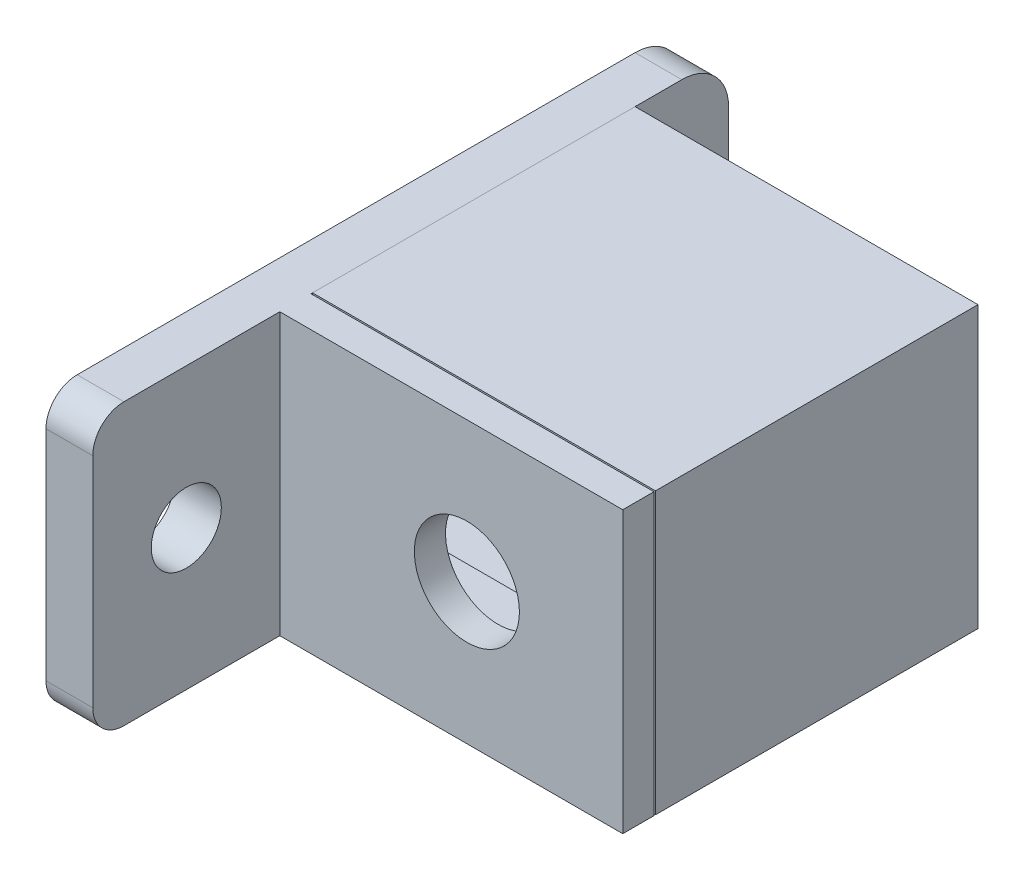
SolidWorks part; units mm, degrees
ref_plane "Front Plane" through (0, 0, 0) normal (0, 0, 1) x (1, 0, 0)
ref_plane "Top Plane" through (0, 0, 0) normal (0, 1, 0) x (1, 0, 0)
ref_plane "Right Plane" through (0, 0, 0) normal (1, 0, 0) x (0, 0, -1)
sketch "Sketch1" plane through (0, 0, 0) normal (1, 0, 0) x (0, 0, -1)
  line L1 (-13.46, 9) -> (-11.46, 9)
  line L2 (-13.46, 9) -> (-13.46, -9)
  line L3 (-13.46, -9) -> (-11.46, -9)
  line L4 (-11.46, 9) -> (-11.46, -9)
  line L5 (0, 0) -> (-11.46, 0) construction
  line L6 (-13.46, -6) -> (-13.46, 6) construction
  line L7 (-13.46, -6) -> (-13.46, 6) construction
  line L8 (4.33, 1.135) -> (4.33, -1.135) construction
  line L9 (4.33, 1.135) -> (4.33, -1.135) construction
  dimension "D1" = 3
  dimension "D2" = 2
extrude "Boss-Extrude1" add sketch "Sketch1" along normal blind 10 and the other way blind 15
sketch "Sketch2" plane through (0, 0, 11.46) normal (0, 0, -1) x (-1, 0, 0)
  line L0 (15, -9) -> (15, 9) construction
  line L1 (15, 9) -> (12, 9)
  line L2 (15, 9) -> (15, -9)
  line L3 (15, -9) -> (12, -9)
  line L4 (12, 9) -> (12, -9)
  line L5 (15, -9) -> (-10, -9) construction
  dimension "D1" = 3
extrude "Boss-Extrude2" add sketch "Sketch2" along normal offset from surface (20.79 mm away) 5 offset beyond the face yes
sketch "Sketch3" plane through (-12, 0, 0) normal (1, 0, 0) x (0, 0, -1)
  line L0 (-11.36, 9) -> (-11.36, 7)
  line L1 (-11.46, 9) -> (-11.46, -9) construction
  line L2 (-11.36, 7) -> (7.33, 7)
  line L3 (7.33, 7) -> (7.33, -7)
  line L4 (9.33, -9) -> (9.33, 9)
  line L5 (9.33, 9) -> (-11.46, 9)
  line L6 (-11.46, 9) -> (-11.46, -9)
  line L7 (-11.46, -9) -> (9.33, -9)
  line L8 (9.33, -9) -> (9.33, 9)
  line L9 (9.33, 9) -> (-11.36, 9)
  line L11 (-11.36, -9) -> (9.33, -9)
  line L12 (7.33, -7) -> (-11.36, -7)
  line L13 (-11.36, -7) -> (-11.36, -9)
  line L14 (7.33, 7) -> (9.33, 7) construction
  dimension "D2" = 0.1
  dimension "D3" = 2
  dimension "D1" = 0
extrude "Boss-Extrude3" add sketch "Sketch3" along normal up to surface (22 mm away) separate body up to face at (10, 0, 12.46)
sketch "Sketch4" plane through (-12, 0, 0) normal (1, 0, 0) x (0, 0, -1)
  line L0 (-11.46, 6.5) -> (-9.46, 6.5)
  line L1 (-11.46, -9) -> (-11.46, 9) construction
  line L2 (-9.46, 6.5) -> (-7.96, 8)
  line L3 (-7.96, 8) -> (-7.96, 4.5)
  line L4 (-7.96, 4.5) -> (-11.46, 4.5)
  line L5 (-11.46, 4.5) -> (-11.46, 6.5)
  line L6 (-11.46, 9) -> (-13.46, 9) construction
  line L7 (0, 0) -> (-5.1966, 0) construction
  line L8 (-7.96, -4.5) -> (-11.46, -4.5)
  line L9 (-7.96, -8) -> (-7.96, -4.5)
  line L10 (-9.46, -6.5) -> (-7.96, -8)
  line L11 (-11.46, -6.5) -> (-9.46, -6.5)
  line L12 (-11.46, -4.5) -> (-11.46, -6.5)
  dimension "D1" = 2
  dimension "D2" = 1.5
  dimension "D3" = 3.5
  dimension "D4" = 45
  dimension "D5" = 1
sketch "Sketch5" plane through (-12, 0, 0) normal (1, 0, 0) x (0, 0, -1)
  line L0 (-9.1014, 7) -> (-7.86, 8.2414)
  line L9 (-11.36, 7) -> (7.33, 7) construction
  line L10 (-7.86, 8.2414) -> (-7.86, 7)
  line L11 (-7.86, 7) -> (-9.1014, 7)
  line L12 (-11.36, 7) -> (-11.46, 7) construction
  line L13 (-11.36, 9) -> (-11.36, 7) construction
  line L14 (-11.46, -9) -> (-11.46, 9) construction
  line L15 (-7.96, 8) -> (-7.86, 8) construction
  line L16 (-9.46, 6.5) -> (-7.96, 8) construction
  line L17 (-7.96, 8) -> (-8.0307, 8.0707) construction
  line L18 (0, 0) -> (-5.0644, 0) construction
  line L19 (-7.86, -8.2414) -> (-7.86, -7)
  line L20 (-9.1014, -7) -> (-7.86, -8.2414)
  line L21 (-7.86, -7) -> (-9.1014, -7)
sketch "Sketch6" plane through (10, 0, 0) normal (1, 0, 0) x (0, 0, -1)
  line L1 (9.33, 9) -> (-11.36, 9)
  line L2 (9.33, 9) -> (9.33, -9)
  line L3 (9.33, -9) -> (-11.36, -9)
  line L4 (-11.36, 9) -> (-11.36, -9)
extrude "Boss-Extrude4" add sketch "Sketch6" against normal blind 3
extrude "Cut-Extrude1" cut sketch "Sketch5" along normal up to surface (19 mm away) up to face at (7, 0, 2.015)
extrude "Boss-Extrude5" add sketch "Sketch4" along normal offset from surface (18.5 mm away) 0.5 up to face at (7, 0, 5.7703)
sketch "Sketch7" plane through (0, 0, -9.33) normal (0, 0, -1) x (-1, 0, 0)
  line L0 (12, 9) -> (12, -9) construction
  circle A0 centre (12, 0) radius 3.75
  dimension "D1" = 7.5
extrude "Cut-Extrude2" cut sketch "Sketch7" against normal through all
sketch "Sketch8" plane through (0, 0, 13.46) normal (0, 0, 1) x (1, 0, 0)
  circle A0 centre (0, 0) radius 2.87 construction
  circle A1 centre (0, 0) radius 2.87 construction
  circle A2 centre (0, 0) radius 3.37
  dimension "D1" = 0.5
extrude "Cut-Extrude3" cut sketch "Sketch8" against normal through all
sketch "Sketch9" plane through (-15, 0, 0) normal (-1, 0, 0) x (0, 0, 1)
  line L0 (-9.33, -9) -> (-12.33, -9)
  line L1 (-9.33, -9) -> (-9.33, 9) construction
  line L2 (-15.33, -6) -> (-15.33, 6)
  line L3 (-12.33, 9) -> (-9.33, 9)
  line L4 (-9.33, 9) -> (-9.33, -9)
  line L5 (-15.33, 6) -> (-9.33, 6) construction
  arc A0 (-12.33, -9) -> (-15.33, -6) centre (-12.33, -6) cw
  arc A1 (-15.33, 6) -> (-12.33, 9) centre (-12.33, 6) cw
  dimension "D1" = 6
extrude "Boss-Extrude6" add sketch "Sketch9" against normal up to surface (3 mm away) up to face at (-12, 0, 7.2043)
sketch "Sketch13" plane through (-15, 0, 0) normal (-1, 0, 0) x (0, 0, 1)
  line L1 (-12.33, 6) -> (-9.33, 6)
  line L2 (-12.33, 6) -> (-12.33, -6)
  line L3 (-12.33, -6) -> (-9.33, -6)
  line L4 (-9.33, 6) -> (-9.33, -6)
  arc A0 (-12.33, 9) -> (-15.33, 6) centre (-12.33, 6) ccw construction
  arc A1 (-15.33, -6) -> (-12.33, -9) centre (-12.33, -6) ccw construction
  dimension "D1" = 3
extrude "Boss-Extrude7" add sketch "Sketch13" along normal blind 3
sketch "Sketch14" plane through (-15, 0, 0) normal (-1, 0, 0) x (0, 0, 1)
  line L0 (13.46, -9) -> (13.46, 9)
  line L1 (13.46, 9) -> (23.46, 9)
  line L2 (25.46, 7) -> (25.46, -7)
  line L3 (23.46, -9) -> (13.46, -9)
  line L4 (25.46, 7) -> (13.46, 7) construction
  arc A0 (23.46, 9) -> (25.46, 7) centre (23.46, 7) cw
  arc A1 (25.46, -7) -> (23.46, -9) centre (23.46, -7) cw
  dimension "D1" = 12
  dimension "D2" = 2
extrude "Boss-Extrude8" add sketch "Sketch14" against normal up to surface (3 mm away) up to face at (-12, 0, 3.9348)
hole_wizard "#8 Clearance Hole1" positions "Sketch16" profile "Sketch17" hole size "#8" standard "ANSI Inch" end condition through all
sketch "Sketch16" plane through (-12, 0, 0) normal (1, 0, 0) x (0, 0, -1)
  line L0 (-13.46, 0) -> (-25.46, 0) construction
  line L1 (-13.46, -9) -> (-13.46, 9) construction
  line L2 (-25.46, 7) -> (-25.46, -7) construction
  point P0 (-19.46, 0)
sketch "Sketch17" plane through (-12, 0, 19.46) normal (0, 1, 0) x (0, 0, -1)
  line L0 (0, 0) -> (0, 6)
  line L1 (0, 6) -> (2.2479, 6)
  line L2 (2.2479, 6) -> (2.2479, 0)
  line L5 (2.2479, 0) -> (0, 0)
  line L11 (0, -6.35) -> (0, 107.95) construction
  dimension "Thru Hole Dia." = 4.4958
  dimension "Thru Hole Depth" = 6
